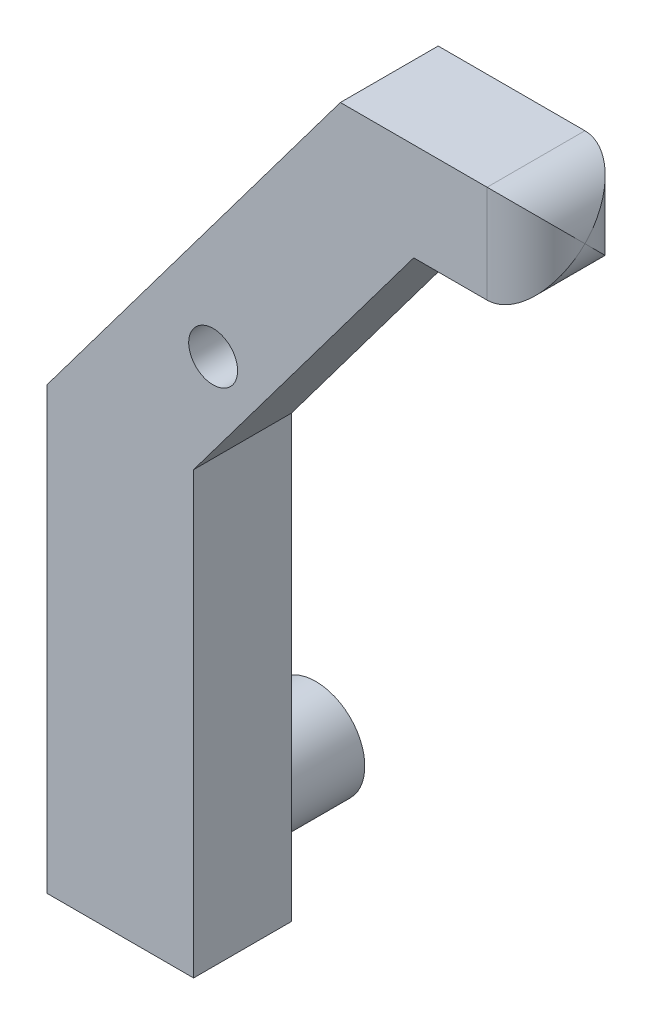
SolidWorks part; units mm, degrees
ref_plane "前视基准面" through (0, 0, 0) normal (0, 0, 1) x (1, 0, 0)
ref_plane "上视基准面" through (0, 0, 0) normal (0, 1, 0) x (1, 0, 0)
ref_plane "右视基准面" through (0, 0, 0) normal (1, 0, 0) x (0, 0, -1)
other "Configuration Table"
sketch "草图4" plane through (0, 0, 0) normal (0, 0, 1) x (1, 0, 0)
  line L0 (0, 0) -> (-30, 0)
  line L1 (-30, 0) -> (-30, 90)
  line L2 (-30, 90) -> (30, 170)
  line L3 (30, 170) -> (70, 170)
  line L4 (70, 170) -> (70, 150)
  line L5 (70, 150) -> (45, 150)
  line L6 (45, 150) -> (0, 90)
  line L7 (0, 90) -> (0, 0)
  point P3 (57.2015, 146.8612)
  point P10 (49.4294, 156.6318)
  point P11 (42.5456, 181.0583)
  point P12 (29.222, 172.1759)
  dimension "D1" = 90
  dimension "D2" = 30
  dimension "D3" = 90
  dimension "D4" = 100
  dimension "D5" = 75
  dimension "D6" = 20
  dimension "D7" = 70
extrude "凸台-拉伸1" add sketch "草图4" along normal blind 20
fillet "圆角2" radius 10 4 edges at (70, 150, 10) (70, 160, 0) (70, 170, 10) (70, 160, 20)
sketch "草图5" plane through (0, 0, 0) normal (0, 0, -1) x (-1, 0, 0)
  line L0 (30, 90) -> (30, 0) construction
  line L1 (0, 0) -> (30, 0)
  line L2 (0, 0) -> (0, 30)
  line L3 (0, 30) -> (30, 30)
  line L4 (30, 0) -> (30, 30)
  line L5 (0, 30) -> (30, 0) construction
  line L6 (30, 30) -> (0, 0)
  circle A0 centre (15, 15) radius 10
  point P10 (0, 30)
  dimension "D2" = 20
  dimension "D1" = 30
extrude "凸台-拉伸2" add sketch "草图5" along normal blind 20 contours L6 L5 A0 | L5 A0 L6 | L5 L6 A0 | A0 L5 L6 region at (-8.9979, 15, 0) region at (-15, 8.9979, 0) region at (-21.0021, 15, 0) region at (-15, 21.0021, 0)
sketch "草图6" plane through (0, 0, 20) normal (0, 0, 1) x (1, 0, 0)
  line L1 (0, 90) -> (45, 150) construction
  line L3 (0, 90) -> (-19.2, 104.4)
  line L4 (30, 170) -> (-30, 90) construction
  circle A0 centre (4, 112) radius 5
  dimension "D1" = 10
  dimension "D2" = 10
  dimension "D3" = 20
extrude "切除-拉伸1" cut sketch "草图6" against normal blind 20 contours A0 region at (4, 112, 20)
